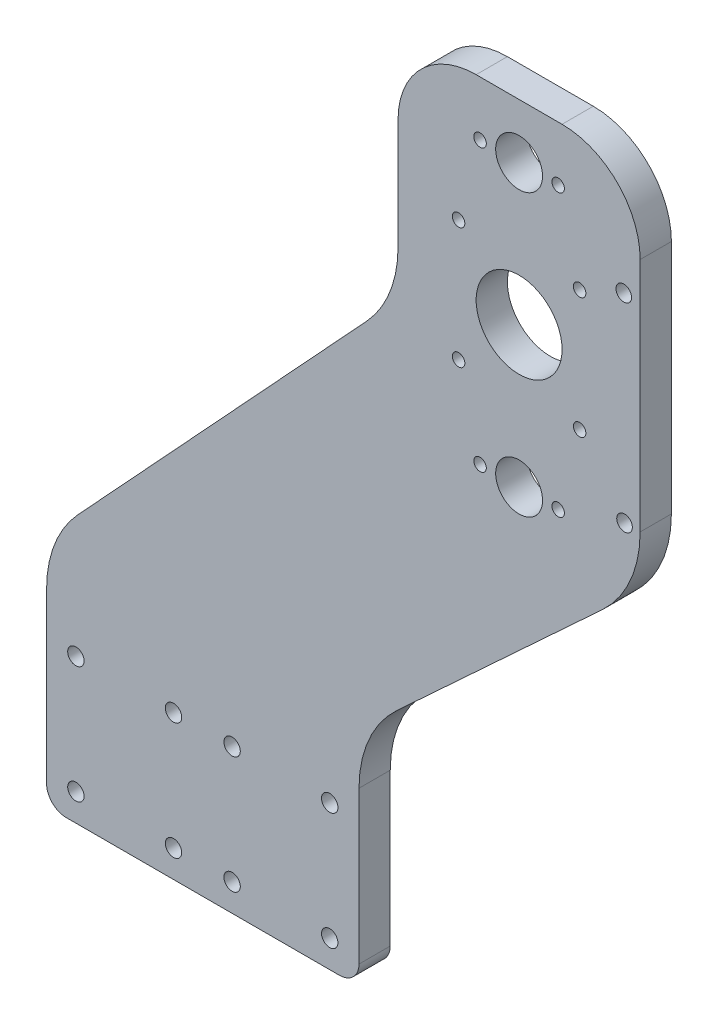
SolidWorks part; units mm, degrees
ref_plane "Front Plane" through (0, 0, 0) normal (0, 0, 1) x (1, 0, 0)
ref_plane "Top Plane" through (0, 0, 0) normal (0, 1, 0) x (1, 0, 0)
ref_plane "Right Plane" through (0, 0, 0) normal (1, 0, 0) x (0, 0, -1)
sketch "Sketch1" plane through (0, 0, 0) normal (0, 0, 1) x (1, 0, 0)
  line L0 (-23.4503, -99.2073) -> (-23.4503, -15.4242) construction
  line L1 (-58.4503, -99.2073) -> (11.5497, -99.2073)
  line L2 (-63.4503, -94.2073) -> (-63.4503, -50.959)
  line L3 (-63.4503, -94.2073) -> (-23.4503, -94.2073) construction
  line L4 (16.5497, -94.2073) -> (16.5497, -55.2061)
  line L5 (46.5497, 118.0426) -> (68.5497, 118.0426)
  line L6 (26.5497, 98.0426) -> (26.5497, 69.7942)
  line L7 (57.5497, 118.0426) -> (57.5497, 32.1026) construction
  line L8 (88.5497, 98.0426) -> (88.5497, 37.6266)
  line L9 (-43.4503, -77.2073) -> (-43.4503, -94.2073) construction
  line L10 (-55.9503, -62.2073) -> (-30.9503, -62.2073) construction
  line L11 (18.5677, 49.4176) -> (-55.4683, -30.5824)
  line L12 (78.9209, 15.6036) -> (26.1784, -33.1831)
  line L13 (-55.9503, -62.2073) -> (-55.9503, -92.2073) construction
  line L14 (-55.9503, -92.2073) -> (-30.9503, -92.2073) construction
  line L15 (-30.9503, -62.2073) -> (-30.9503, -92.2073) construction
  line L16 (-55.9503, -62.2073) -> (-30.9503, -92.2073) construction
  line L17 (-55.9503, -92.2073) -> (-30.9503, -62.2073) construction
  line L18 (57.5497, 104.0426) -> (57.5497, 32.1026) construction
  line L20 (42.0497, 52.5726) -> (73.0497, 52.5726) construction
  line L21 (42.0497, 52.5726) -> (42.0497, 83.5726) construction
  line L22 (42.0497, 83.5726) -> (73.0497, 83.5726) construction
  line L23 (73.0497, 52.5726) -> (73.0497, 83.5726) construction
  line L24 (42.0497, 52.5726) -> (73.0497, 83.5726) construction
  line L25 (42.0497, 83.5726) -> (73.0497, 52.5726) construction
  arc A0 (78.9209, 15.6036) -> (88.5497, 37.6266) centre (58.5497, 37.6266) ccw
  arc A1 (18.5677, 49.4176) -> (26.5497, 69.7942) centre (-3.4503, 69.7942) ccw
  arc A2 (16.5497, -55.2061) -> (26.1784, -33.1831) centre (46.5497, -55.2061) cw
  arc A3 (-63.4503, -50.959) -> (-55.4683, -30.5824) centre (-33.4503, -50.959) cw
  arc A4 (88.5497, 98.0426) -> (68.5497, 118.0426) centre (68.5497, 98.0426) ccw
  arc A5 (46.5497, 118.0426) -> (26.5497, 98.0426) centre (46.5497, 98.0426) ccw
  arc A6 (16.5497, -94.2073) -> (11.5497, -99.2073) centre (11.5497, -94.2073) cw
  arc A7 (-58.4503, -99.2073) -> (-63.4503, -94.2073) centre (-58.4503, -94.2073) cw
  circle A8 centre (-55.9503, -62.2073) radius 2.1
  circle A9 centre (-30.9503, -62.2073) radius 2.1
  circle A10 centre (-30.9503, -92.2073) radius 2.1
  circle A11 centre (-55.9503, -92.2073) radius 2.1
  circle A12 centre (9.0497, -92.2073) radius 2.1
  circle A13 centre (-15.9503, -92.2073) radius 2.1
  circle A14 centre (-15.9503, -62.2073) radius 2.1
  circle A15 centre (9.0497, -62.2073) radius 2.1
  circle A16 centre (57.5497, 104.0426) radius 6
  circle A17 centre (57.5497, 32.1026) radius 6
  circle A18 centre (57.5497, 68.0726) radius 11
  circle A19 centre (42.0497, 83.5726) radius 1.6
  circle A20 centre (73.0497, 83.5726) radius 1.6
  circle A21 centre (73.0497, 52.5726) radius 1.6
  circle A22 centre (42.0497, 52.5726) radius 1.6
  circle A23 centre (84.5497, 37.6266) radius 2
  circle A24 centre (84.3518, 88.5185) radius 2
  circle A25 centre (47.5497, 104.0426) radius 1.6
  circle A26 centre (47.5497, 32.1026) radius 1.6
  circle A27 centre (67.5497, 104.0426) radius 1.6
  circle A28 centre (67.5497, 32.1026) radius 1.6
  point P0 (0, 0)
  point P1 (57.5497, 82.2289)
  point P15 (26.5497, 58.0426)
  point P20 (-63.4503, -39.2073)
  point P23 (88.5497, 118.0426)
  point P26 (26.5497, 118.0426)
  point P29 (16.5497, -99.2073)
  point P32 (-63.4503, -99.2073)
  point P35 (-43.4503, -77.2073)
  dimension "D5" = 30
  dimension "D6" = 20
  dimension "D7" = 5
  dimension "D14" = 71.94
  dimension "D12" = 31
  dimension "D17" = 4
  dimension "D18" = 10
  dimension "D19" = 10
  dimension "D1" = 80
  dimension "D2" = 22
  dimension "D3" = 90
  dimension "D4" = 60
  dimension "D8" = 25
  dimension "D9" = 60
  dimension "D10" = 22
  dimension "D11" = 80
  dimension "D13" = 30
  dimension "D15" = 14
  dimension "D16" = 31
extrude "Boss-Extrude1" add sketch "Sketch1" along normal blind 8
